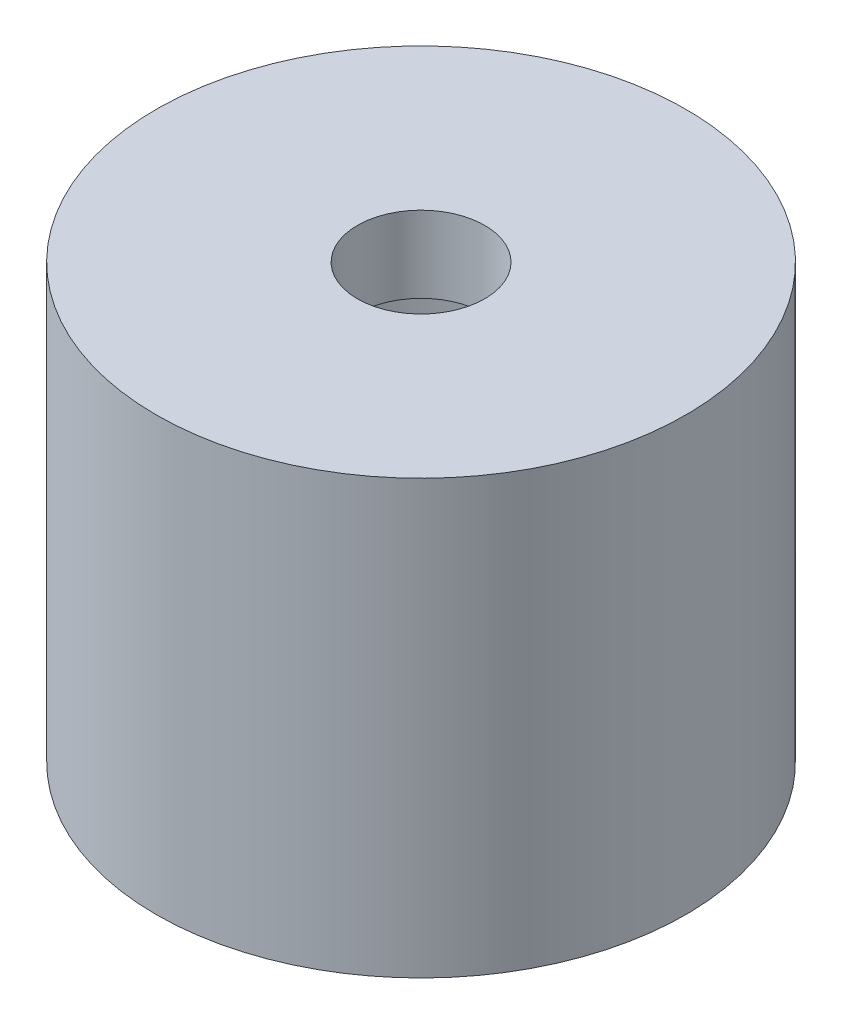
SolidWorks part; units mm, degrees
ref_plane "Front Plane" through (0, 0, 0) normal (0, 0, 1) x (1, 0, 0)
ref_plane "Top Plane" through (0, 0, 0) normal (0, 1, 0) x (1, 0, 0)
ref_plane "Right Plane" through (0, 0, 0) normal (1, 0, 0) x (0, 0, -1)
sketch "Sketch1" plane through (0, 0, 0) normal (0, 1, 0) x (1, 0, 0)
  circle A0 centre (0, 0) radius 13.97
  circle A2 centre (0, 0) radius 16.51
  dimension "D1" = 27.94
  dimension "D2" = 2.54
extrude "Boss-Extrude1" add sketch "Sketch1" against normal blind 22.225
extrude "Boss-Extrude2" add sketch "Sketch1<2>" along normal blind 4.7625 contours A2
sketch "Sketch1<2>" plane through (0, 0, 0) normal (0, 1, 0) x (1, 0, 0) same geometry as "Sketch1"
sketch "Sketch8" plane through (0, 4.7625, 0) normal (0, 1, 0) x (1, 0, 0)
  point P0 (0, 0)
hole_wizard "5/16 (0.3125) Diameter Hole1" positions "Sketch8" profile "Sketch9" hole size "5/16" standard "ANSI Inch" end condition up to next
sketch "Sketch9" plane through (0, 4.7625, 0) normal (1, 0, 0) x (0, 0, 1)
  line L0 (0, 0) -> (0, 4.7625)
  line L1 (0, 4.7625) -> (3.9687, 4.7625)
  line L2 (3.9687, 4.7625) -> (3.9688, 0)
  line L5 (3.9688, 0) -> (0, 0)
  line L11 (0, -6.35) -> (0, 107.95) construction
  dimension "Thru Hole Dia." = 7.9375
  dimension "Thru Hole Depth" = 4.7625
